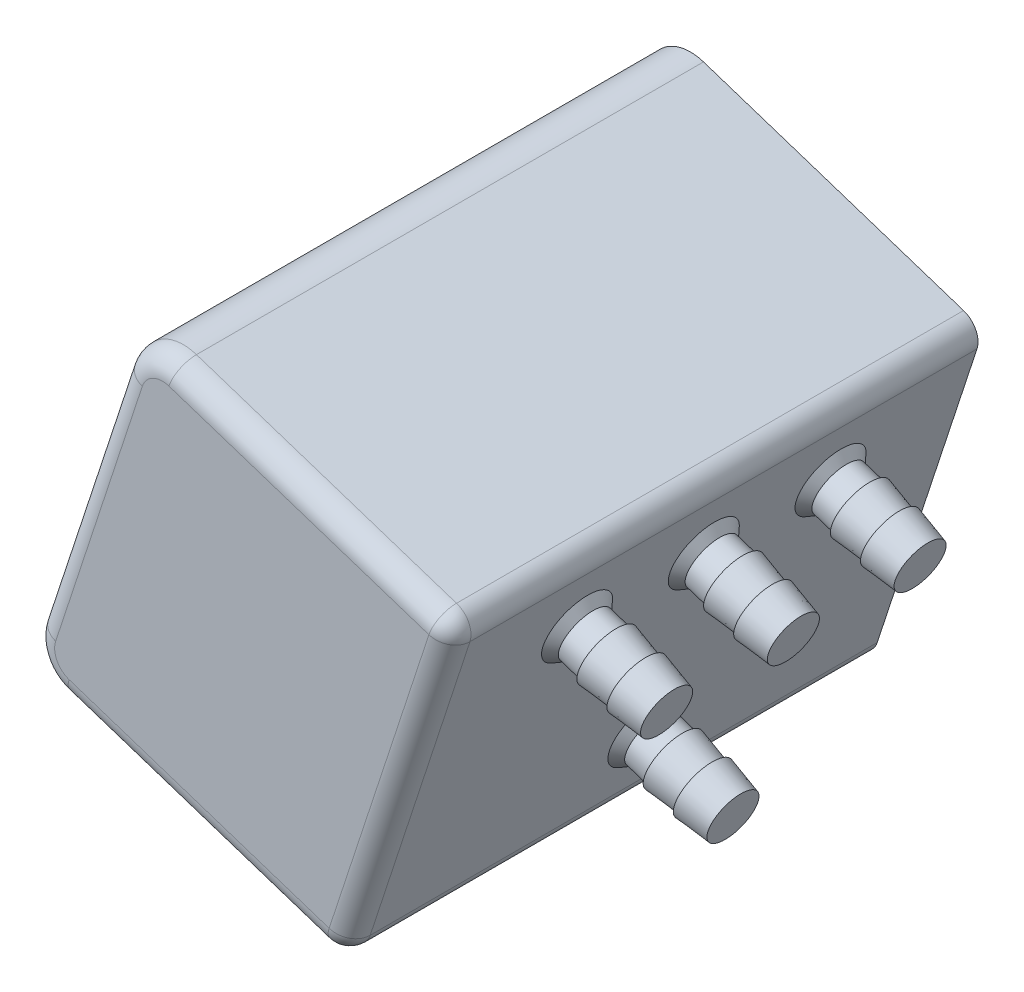
SolidWorks part; units mm, degrees
material "PET"
ref_plane "Front Plane" through (0, 0, 0) normal (0, 0, 1) x (1, 0, 0)
ref_plane "Top Plane" through (0, 0, 0) normal (0, 1, 0) x (1, 0, 0)
ref_plane "Right Plane" through (0, 0, 0) normal (1, 0, 0) x (0, 0, -1)
sketch "Sketch1" plane through (0, 0, 0) normal (0, 0, 1) x (1, 0, 0)
  line L0 (290.2809, 502.98) -> (307.3073, 554.8844) construction
  line L1 (290.2809, 502.98) -> (307.3073, 554.8844)
  line L2 (307.3073, 554.8844) -> (417.2514, 518.8189) construction
  line L4 (307.3073, 554.8844) -> (355.5766, 539.0504)
  line L5 (338.5502, 487.146) -> (290.2809, 502.98)
  line L6 (355.5766, 539.0504) -> (338.5502, 487.146)
  line L7 (247.2747, 82.1423) -> (332.9427, 343.2977) construction
  line L10 (316.9169, 494.2424) -> (290.2809, 502.98) construction
  dimension "D1" = 50.8
extrude "Boss-Extrude1" add sketch "Sketch1" along normal offset from surface (79.6427 mm away) 3.175
fillet "Fillet1" radius 6.35 2 edges at (307.3073, 554.8844, 39.8213) (290.2809, 502.98, 39.8213)
fillet "Fillet2" radius 3.175 8 edges at (347.0634, 513.0982, 79.6427) (317.4323, 494.0734, 79.6427) (292.6278, 504.1675, 79.6427) (298.7941, 528.9322, 79.6427) (308.4948, 552.5375, 79.6427) (334.4588, 545.9778, 79.6427) (355.5766, 539.0504, 39.8213) (338.5502, 487.146, 39.8213)
sketch "Sketch5" plane through (161.3834, -52.9394, 0) normal (0.9502, -0.3117, 0) x (0, 0, -1)
  line L0 (-38.2338, 571.5765) -> (-38.2338, 619.8522) construction
  line L3 (-76.4677, 610.3272) -> (-38.2338, 610.3272) construction
  line L5 (0, 571.5765) -> (0, 619.8522) construction
  line L6 (-38.2338, 610.3272) -> (0, 610.3272) construction
  line L8 (-76.4677, 619.8522) -> (-76.4677, 571.5765) construction
  line L9 (0, 619.8522) -> (-76.4677, 619.8522) construction
  line L10 (-76.4677, 571.5765) -> (0, 571.5765) construction
  point P2 (0, 0)
  point P7 (-38.2338, 610.3272)
  point P11 (-38.2338, 581.1015)
  point P15 (-57.3508, 610.3272)
  point P17 (-19.1169, 610.3272)
  point P33 (-19.1169, 610.3272)
  dimension "D1" = 9.525
  dimension "D2" = 9.525
ref_plane "Plane1" through (0, 0, 38.2338) normal (0, 0, 1) x (1, 0, 0)
sketch "Sketch6" plane through (0, 0, 38.2338) normal (0, 0, 1) x (1, 0, 0)
  line L0 (342.5087, 499.2133) -> (365.0021, 491.8347)
  line L1 (339.5398, 490.1628) -> (354.587, 536.0336) construction
  line L3 (365.0021, 491.8347) -> (366.1422, 495.31)
  line L13 (348.2368, 501.3861) -> (343.7087, 502.8715)
  line L14 (348.3952, 501.8688) -> (348.2368, 501.3861)
  line L15 (352.7132, 499.8671) -> (348.3952, 501.8688)
  line L16 (352.8715, 500.3498) -> (352.7132, 499.8671)
  line L17 (357.1895, 498.3481) -> (352.8715, 500.3498)
  line L18 (357.3479, 498.8308) -> (357.1895, 498.3481)
  line L19 (361.6659, 496.8291) -> (357.3479, 498.8308)
  line L20 (361.8242, 497.3118) -> (361.6659, 496.8291)
  line L21 (366.1422, 495.31) -> (361.8242, 497.3118)
  line L22 (343.7087, 502.8715) -> (342.5087, 499.2133)
  dimension "D1" = 23.6728
  dimension "D2" = 3.6576
  dimension "D3" = 6.71
  dimension "D4" = 4.318
  dimension "D5" = 0.508
revolve "Revolve1" add sketch "Sketch6" angle 360 about L0
sketch "Sketch7" plane through (183.8769, -60.318, 0) normal (0.9502, -0.3117, 0) x (0, 0, -1)
  circle A0 centre (-38.2338, 581.1015) radius 4.2618 construction
  circle A1 centre (-38.2338, 581.1015) radius 4.2618
extrude "Cut-Extrude1" cut sketch "Sketch7" against normal up to surface (9.4536 mm away) up to face at (354.8495, 491.2145, 38.2338)
chamfer "Chamfer1" distance 1.27 angle 45 1 edges at (341.3086, 495.5551, 38.2338)
pattern_sketch "Sketch-Pattern2" of "Chamfer1", "Revolve1", "Cut-Extrude1" driven by "Sketch5"
hole_wizard "Hole1" positions "Sketch8" profile "Sketch9" legacy
sketch "Sketch8" plane through (0, 0, 0) normal (0, 0, -1) x (-1, 0, 0)
  line L2 (-347.0634, 513.0982) -> (-324.4371, 520.5204) construction
  line L3 (-339.5398, 490.1628) -> (-354.587, 536.0336) construction
  line L4 (-324.4371, 520.5204) -> (-332.9504, 546.4726) construction
  line L5 (-352.5598, 540.04) -> (-313.341, 552.9051) construction
  line L7 (-296.3145, 501.0007) -> (-335.5333, 488.1356) construction
  point P9 (-332.4685, 499.1653)
  point P24 (-343.5572, 532.9688)
  point P26 (-305.3171, 508.072)
  point P27 (-316.4058, 541.8754)
  dimension "D1" = 9.525
  dimension "D2" = 9.525
sketch "Sketch9" plane through (332.4685, 499.1653, 0) normal (1, 0, 0) x (0, 1, 0)
  line L0 (0, 0) -> (0, 4.699)
  line L1 (0, 4.699) -> (2.8702, 4.699)
  line L2 (2.8702, 4.699) -> (2.9972, 0)
  line L3 (2.9972, 0) -> (0, 0)
  line L4 (0, 110) -> (0, -10) construction
  dimension "Minor Diameter" = 5.7404
  dimension "Depth" = 4.699
  dimension "Major Diameter" = 5.9944
hole_wizard "#8 Clearance Hole1" positions "Sketch10" profile "Sketch11" hole size "#8" standard "ANSI Inch"
sketch "Sketch10" plane through (0, 0, 0) normal (0, 0, -1) x (-1, 0, 0)
  point P0 (-332.4685, 499.1653)
  point P3 (-343.5572, 532.9688)
  point P6 (-316.4058, 541.8754)
  point P9 (-305.3171, 508.072)
sketch "Sketch11" plane through (332.4685, 499.1653, 0) normal (1, 0, 0) x (0, 1, 0)
  line L0 (0, 0) -> (0, 14.1766)
  line L1 (0, 14.1766) -> (2.4574, 12.7)
  line L2 (2.4574, 12.7) -> (2.4574, 0)
  line L5 (2.4574, 0) -> (0, 0)
  line L10 (0, 14.1766) -> (-2.4575, 12.7) construction
  line L11 (0, -6.35) -> (0, 107.95) construction
  dimension "Hole Dia." = 4.9149
  dimension "Hole Depth" = 12.7
  dimension "Drill Angle" = 118
